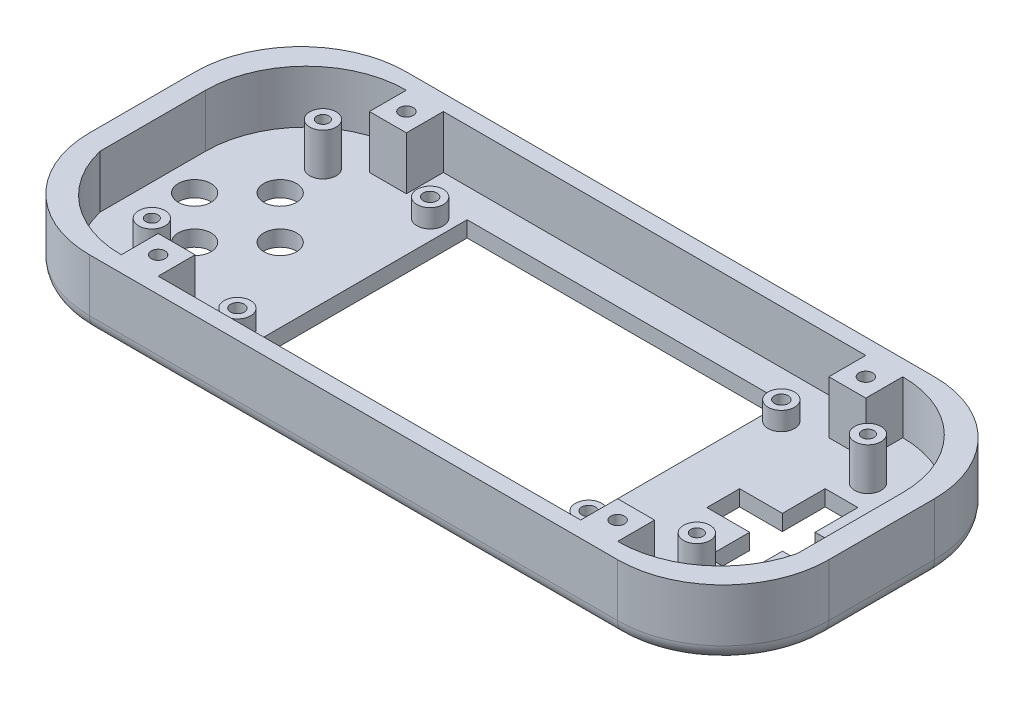
SolidWorks part; units mm, degrees
ref_plane "Front Plane" through (0, 0, 0) normal (0, 0, 1) x (1, 0, 0)
ref_plane "Top Plane" through (0, 0, 0) normal (0, 1, 0) x (1, 0, 0)
ref_plane "Right Plane" through (0, 0, 0) normal (1, 0, 0) x (0, 0, -1)
sketch "Sketch1" plane through (0, 0, 0) normal (0, 1, 0) x (1, 0, 0)
  line L0 (70, 10) -> (70, -10)
  line L1 (-50, 30) -> (50, 30)
  line L2 (-70, 10) -> (-70, -10)
  line L3 (-50, -30) -> (50, -30)
  line L5 (-50, 30) -> (50, -30) construction
  line L6 (-50, -30) -> (50, 30) construction
  arc A0 (-50, 30) -> (-70, 10) centre (-50, 10) ccw
  arc A1 (50, 30) -> (70, 10) centre (50, 10) cw
  arc A2 (-50, -30) -> (-70, -10) centre (-50, -10) cw
  arc A3 (50, -30) -> (70, -10) centre (50, -10) ccw
  point P0 (0, 0)
  dimension "D1" = 100
extrude "Boss-Extrude1" add sketch "Sketch1" along normal blind 3
sketch "Sketch2" plane through (0, 3, 0) normal (0, 1, 0) x (1, 0, 0)
  line L0 (-50, -30) -> (50, -30) construction
  line L1 (-47, 27) -> (47, 27)
  line L2 (-50, 30) -> (50, 30)
  line L3 (-47, -27) -> (47, -27)
  line L4 (70, 10) -> (70, -10)
  line L5 (-47, 27) -> (47, -27) construction
  line L6 (-47, -27) -> (47, 27) construction
  line L7 (-50, -30) -> (50, -30)
  line L8 (66, 8) -> (66, -12)
  line L9 (-50, 30) -> (50, -30) construction
  line L10 (-50, -30) -> (50, 30) construction
  line L11 (-70, 10) -> (-70, -10)
  line L13 (-66, 8) -> (-66, -12)
  arc A0 (-50, 30) -> (-70, 10) centre (-50, 10) ccw
  arc A1 (50, 30) -> (70, 10) centre (50, 10) cw
  arc A2 (-50, -30) -> (-70, -10) centre (-50, -10) cw
  arc A3 (50, -30) -> (70, -10) centre (50, -10) ccw
  arc A4 (47, 27) -> (66, 8) centre (47, 8) cw
  arc A5 (47, -27) -> (66, -12) centre (47, -7.4667) ccw
  arc A6 (-47, 27) -> (-66, 8) centre (-47, 8) ccw
  arc A7 (-47, -27) -> (-66, -12) centre (-47, -7.4667) cw
  point P0 (0, 0)
  point P8 (0, 0)
  line M6 (50, 30) -> (-50, 30)
  line M8 (-50, -30) -> (50, -30)
  dimension "D3" = 100
  dimension "D4" = 60
  dimension "D5" = 20
  dimension "D1" = 54
  dimension "D2" = 94
  dimension "D6" = 54
  dimension "D7" = 20
  dimension "D8" = 4
  dimension "D9" = 4
  dimension "D10" = 3
  dimension "D11" = 3
extrude "Boss-Extrude2" add sketch "Sketch2" along normal blind 10 contours L3 M8 | L1 M6 region at (0, 3, -28.4768)
sketch "Sketch3" plane through (0, 3, 0) normal (0, 1, 0) x (1, 0, 0)
  line L1 (-30, 21.5) -> (30, 21.5)
  line L2 (-30, 21.5) -> (-30, -21.5)
  line L3 (-30, -21.5) -> (30, -21.5)
  line L4 (30, 21.5) -> (30, -21.5)
  line L5 (-30, 21.5) -> (30, -21.5) construction
  line L6 (-30, -21.5) -> (30, 21.5) construction
  point P0 (0, 0)
  dimension "D1" = 43
  dimension "D2" = 60
extrude "Cut-Extrude1" cut sketch "Sketch3" against normal blind 5
sketch "Sketch4" plane through (0, 3, 0) normal (0, 1, 0) x (1, 0, 0)
  line L0 (30, 21.5) -> (-30, 21.5) construction
  line L1 (-30, 21.5) -> (-30, -21.5) construction
  line L2 (-30, -21.5) -> (30, -21.5) construction
  line L3 (30, -21.5) -> (30, 21.5) construction
  circle A0 centre (-33.75, 18.25) radius 2.5
  circle A1 centre (-33.75, -18.25) radius 2.5
  circle A2 centre (32.75, -18.25) radius 2.5
  circle A3 centre (32.75, 18.25) radius 2.5
  dimension "D1" = 5
  dimension "D4" = 5
  dimension "D5" = 3.25
  dimension "D7" = 5
  dimension "D10" = 5
  dimension "D2" = 3.25
  dimension "D3" = 3.75
  dimension "D6" = 3.75
  dimension "D8" = 3.25
  dimension "D9" = 2.75
  dimension "D11" = 2.75
  dimension "D12" = 3.25
extrude "Boss-Extrude3" add sketch "Sketch4" along normal blind 3.5
sketch "Sketch5" plane through (0, 6.5, 0) normal (0, 1, 0) x (1, 0, 0)
  circle A0 centre (-33.75, -18.25) radius 1.3
  dimension "D1" = 2.6
extrude "Cut-Extrude2" cut sketch "Sketch5" against normal blind 4.5
sketch "Sketch6" plane through (0, 6.5, 0) normal (0, 1, 0) x (1, 0, 0)
  circle A0 centre (-33.75, 18.25) radius 1.3
  dimension "D1" = 2.6
extrude "Cut-Extrude3" cut sketch "Sketch6" against normal blind 4.5
sketch "Sketch7" plane through (0, 6.5, 0) normal (0, 1, 0) x (1, 0, 0)
  circle A0 centre (32.75, 18.25) radius 1.3
  dimension "D1" = 2.6
extrude "Cut-Extrude4" cut sketch "Sketch7" against normal blind 4.5
sketch "Sketch8" plane through (0, 6.5, 0) normal (0, 1, 0) x (1, 0, 0)
  circle A0 centre (32.75, -18.25) radius 1.3
  dimension "D1" = 2.6
extrude "Cut-Extrude5" cut sketch "Sketch8" against normal blind 4.5
sketch "Sketch9" plane through (0, 3, 0) normal (0, 1, 0) x (1, 0, 0)
  line L0 (62.3, 3.2) -> (54.2, 3.2)
  line L1 (-30, 21.5) -> (-30, -21.5) construction
  line L3 (-47, -27) -> (47, -27) construction
  line L4 (30, 21.5) -> (30, -21.5) construction
  line L5 (46.1, 3.2) -> (39.9, 3.2)
  line L6 (62.3, -3) -> (54.2, -3)
  line L8 (54.2, -4.9) -> (54.2, -11.1)
  line L9 (54.2, -11.1) -> (48, -11.1)
  line L10 (48, -4.9) -> (48, -11.1)
  line L11 (54.2, -4.9) -> (48, -11.1) construction
  line L12 (54.2, -11.1) -> (48, -4.9) construction
  line L13 (46.1, -3) -> (39.9, -3)
  line L14 (39.9, 3.2) -> (39.9, -3)
  line L15 (46.1, 3.2) -> (39.9, -3) construction
  line L16 (46.1, -3) -> (39.9, 3.2) construction
  line L18 (62.3, 3.2) -> (62.3, -3)
  line L23 (54.2, 11.3) -> (48, 11.3)
  line L24 (54.2, 11.3) -> (54.2, 5.1)
  line L26 (48, 11.3) -> (48, 5.1)
  line L27 (54.2, 11.3) -> (48, 5.1) construction
  line L28 (54.2, 5.1) -> (48, 11.3) construction
  line L30 (54.2, -3) -> (54.2, -4.9)
  line L32 (54.2, 3.2) -> (54.2, 5.1)
  line L33 (48, 5.1) -> (48, 3.2)
  line L34 (48, 3.2) -> (46.1, 3.2)
  line L35 (46.1, -3) -> (48, -3)
  line L36 (48, -3) -> (48, -4.9)
  circle A4 centre (-44, 0.1) radius 3.1
  circle A5 centre (-52.1, 8.2) radius 3.1
  circle A6 centre (-60.2, 0.1) radius 3.1
  circle A7 centre (-52.1, -8) radius 3.1
  dimension "D3" = 9.9
  dimension "D4" = 6.2
  dimension "D5" = 6.2
  dimension "D6" = 8.1
  dimension "D7" = 6.2
  dimension "D8" = 6.2
  dimension "D9" = 6.2
  dimension "D10" = 6.2
  dimension "D11" = 8.1
  dimension "D12" = 6.2
  dimension "D13" = 6.2
  dimension "D14" = 6.2
  dimension "D15" = 6.2
  dimension "D16" = 8.1
  dimension "D17" = 14
  dimension "D18" = 8.1
  dimension "D19" = 8.1
  dimension "D20" = 8.1
  dimension "D21" = 8.1
  dimension "D22" = 8.1
  dimension "D23" = 1.9
  dimension "D24" = 19
  dimension "D25" = 8.1
  dimension "D26" = 11.4551
extrude "Cut-Extrude6" cut sketch "Sketch9" against normal blind 4.5
sketch "Sketch10" plane through (0, 3, 0) normal (0, 1, 0) x (1, 0, 0)
  line L1 (-47, -27) -> (47, -27) construction
  line L2 (30, -21.5) -> (30, 21.5) construction
  line L3 (-30, 21.5) -> (-30, -21.5) construction
  circle A0 centre (-52.1, -16.1) radius 2.5
  circle A1 centre (-52.1, 16.3) radius 2.5
  circle A2 centre (51.1, 16.3) radius 2.5
  circle A3 centre (51.1, -16.1) radius 2.5
  circle A4 centre (-52.1, -8) radius 3.1 construction
  circle A5 centre (-52.1, 8.2) radius 3.1 construction
  circle A6 centre (-52.1, 16.3) radius 1.15
  circle A7 centre (-52.1, -16.1) radius 1.15
  circle A8 centre (51.1, -16.1) radius 1.15
  circle A9 centre (51.1, 16.3) radius 1.15
  dimension "D1" = 5
  dimension "D2" = 5
  dimension "D3" = 5
  dimension "D4" = 5
  dimension "D5" = 8.1
  dimension "D6" = 8.1
  dimension "D7" = 0
  dimension "D8" = 0
  dimension "D9" = 22.1
  dimension "D10" = 10.9
  dimension "D11" = 2.3
  dimension "D12" = 2.3
  dimension "D13" = 2.3
  dimension "D14" = 2.3
  dimension "D15" = 21.1
  dimension "D16" = 21.1
extrude "Boss-Extrude4" add sketch "Sketch10" along normal blind 8
sketch "Sketch12" plane through (0, 3, 0) normal (0, 1, 0) x (1, 0, 0)
  line L0 (-47, -27) -> (47, -27) construction
  line L1 (-47, 27) -> (-40, 27)
  line L2 (-47, 27) -> (-47, 20)
  line L3 (-47, 20) -> (-40, 20)
  line L4 (-40, 27) -> (-40, 20)
  line L5 (-47, -27) -> (-40, -27)
  line L6 (-47, -27) -> (-47, -20)
  line L7 (-47, -20) -> (-40, -20)
  line L8 (-40, -27) -> (-40, -20)
  line L9 (47, -27) -> (40, -27)
  line L10 (47, -27) -> (47, -20)
  line L11 (47, -20) -> (40, -20)
  line L12 (40, -27) -> (40, -20)
  line L13 (47, 27) -> (40, 27)
  line L14 (47, 27) -> (47, 20)
  line L15 (47, 20) -> (40, 20)
  line L16 (40, 27) -> (40, 20)
  line L17 (-47, 27) -> (47, 27) construction
  dimension "D1" = 7
  dimension "D2" = 7
  dimension "D3" = 7
  dimension "D4" = 7
  dimension "D5" = 7
  dimension "D6" = 7
  dimension "D7" = 7
  dimension "D8" = 7
  dimension "D9" = 0
  dimension "D10" = 0
  dimension "D11" = 0
  dimension "D12" = 0
  dimension "D13" = 0
  dimension "D14" = 0
extrude "Boss-Extrude5" add sketch "Sketch12" along normal blind 10
fillet "Fillet1" radius 3 8 edges at (-64.1421, 0, 24.1421) (-64.1421, 0, -24.1421) (-70, 0, 0) (0, 0, 30) (64.1421, 0, 24.1421) (70, 0, 0) (64.1421, 0, -24.1421) (0, 0, -30)
sketch "Sketch13" plane through (0, 13, 0) normal (0, 1, 0) x (1, 0, 0)
  line L0 (47, 20) -> (47, 27) construction
  line L1 (40, 20) -> (47, 20) construction
  line L2 (47, -27) -> (47, -20) construction
  line L3 (47, -20) -> (40, -20) construction
  line L4 (-40, -27) -> (-40, -20) construction
  line L5 (-40, -20) -> (-47, -20) construction
  line L6 (-47, 20) -> (-40, 20) construction
  line L7 (-47, 27) -> (-47, 20) construction
  circle A0 centre (-43.5, 23.5) radius 1.3
  circle A1 centre (-43.5, -23.5) radius 1.3
  circle A2 centre (43.5, -23.5) radius 1.3
  circle A3 centre (43.5, 23.5) radius 1.3
  dimension "D1" = 2.6
  dimension "D2" = 2.6
  dimension "D3" = 2.6
  dimension "D4" = 2.6
  dimension "D7" = 3.5
  dimension "D8" = 3.5
  dimension "D9" = 3.5
  dimension "D11" = 3.5
  dimension "D12" = 3.5
  dimension "D5" = 3.5
  dimension "D6" = 3.5
  dimension "D10" = 3.5
extrude "Cut-Extrude7" cut sketch "Sketch13" against normal blind 9
